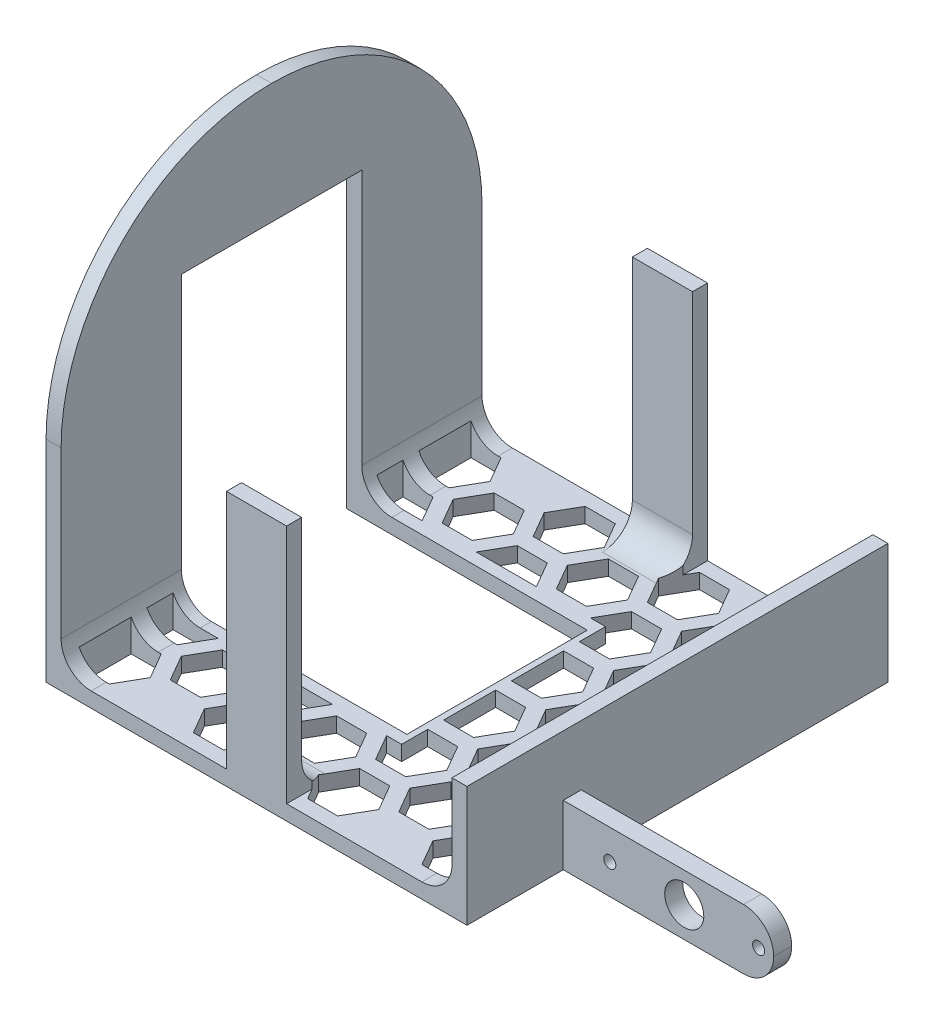
SolidWorks part; units mm, degrees
ref_plane "Front Plane" through (0, 0, 0) normal (0, 0, 1) x (1, 0, 0)
ref_plane "Top Plane" through (0, 0, 0) normal (0, 1, 0) x (1, 0, 0)
ref_plane "Right Plane" through (0, 0, 0) normal (1, 0, 0) x (0, 0, -1)
sketch "Sketch1" plane through (0, 0, 0) normal (0, 1, 0) x (1, 0, 0)
  line L1 (-35, -35) -> (35, -35)
  line L2 (-35, -35) -> (-35, 35)
  line L3 (-35, 35) -> (35, 35)
  line L4 (35, -35) -> (35, 35)
  line L5 (-35, -35) -> (35, 35) construction
  line L6 (-35, 35) -> (35, -35) construction
  point P0 (0, 0)
  dimension "D1" = 70
  dimension "D2" = 70
extrude "Boss-Extrude1" add sketch "Sketch1" along normal blind 70
sketch "Sketch2" plane through (0, 70, 0) normal (0, 1, 0) x (1, 0, 0)
  line L1 (-32.5, -32.5) -> (32.5, -32.5)
  line L2 (-32.5, -32.5) -> (-32.5, 32.5)
  line L3 (-32.5, 32.5) -> (32.5, 32.5)
  line L4 (32.5, -32.5) -> (32.5, 32.5)
  line L5 (-32.5, -32.5) -> (32.5, 32.5) construction
  line L6 (-32.5, 32.5) -> (32.5, -32.5) construction
  point P0 (0, 0)
  dimension "D1" = 65
  dimension "D2" = 65
extrude "Cut-Extrude1" cut sketch "Sketch2" against normal blind 67.5
sketch "Sketch3" plane through (35, 0, 0) normal (1, 0, 0) x (0, 0, -1)
  line L0 (-35, 70) -> (35, 70) construction
  line L1 (-32.5, 70) -> (32.5, 70)
  line L2 (-32.5, 70) -> (-32.5, 20)
  line L3 (-32.5, 20) -> (32.5, 20)
  line L4 (32.5, 70) -> (32.5, 20)
  line L5 (-35, 70) -> (-35, 0) construction
  dimension "D1" = 65
  dimension "D2" = 50
  dimension "D3" = 2.5
extrude "Cut-Extrude2" cut sketch "Sketch3" against normal blind 65
sketch "Sketch4" plane through (-35, 0, 0) normal (-1, 0, 0) x (0, 0, 1)
  line L0 (-35, 0) -> (35, 0) construction
  line L1 (-15, 0) -> (15, 0)
  line L2 (-15, 0) -> (-15, 50)
  line L3 (-15, 50) -> (15, 50)
  line L4 (15, 0) -> (15, 50)
  line L5 (-35, 70) -> (-35, 0) construction
  dimension "D1" = 30
  dimension "D2" = 20
  dimension "D3" = 50
extrude "Cut-Extrude3" cut sketch "Sketch4" against normal blind 40 and the other way blind 70
sketch "Sketch7" plane through (35, 0, 0) normal (1, 0, 0) x (0, 0, -1)
  line L0 (-35, 0) -> (35, 0) construction
  line L1 (-16, 0) -> (-19, 0)
  line L2 (-16, 0) -> (-16, 10)
  line L3 (-16, 10) -> (-19, 10)
  line L4 (-19, 0) -> (-19, 10)
  point P6 (0, 0)
  dimension "D1" = 3
  dimension "D2" = 16
  dimension "D3" = 10
extrude "Boss-Extrude3" add sketch "Sketch7" along normal blind 35
sketch "Sketch11" plane through (0, 0, -35) normal (0, 0, -1) x (-1, 0, 0)
  line L1 (-32.5, 2.5) -> (-5, 2.5)
  line L2 (-32.5, 2.5) -> (-32.5, 20)
  line L3 (-32.5, 82.5) -> (-5, 82.5)
  line L4 (-5, 2.5) -> (-5, 42.5)
  line L5 (35, 70) -> (35, 0) construction
  line L6 (32.5, 2.5) -> (5, 2.5)
  line L7 (32.5, 2.5) -> (32.5, 82.5)
  line L8 (32.5, 82.5) -> (5, 82.5)
  line L9 (5, 2.5) -> (5, 42.5)
  line L10 (-35, 70) -> (-35, 0) construction
  line L11 (-35, 0) -> (35, 0) construction
  line L12 (-32.5, 20) -> (-37.722, 20)
  line L13 (-37.722, 20) -> (-37.722, 82.5)
  line L14 (-37.722, 82.5) -> (-32.5, 82.5)
  line L15 (-5, 82.5) -> (5, 82.5)
  line L16 (-5, 42.5) -> (5, 42.5)
  dimension "D1" = 80
  dimension "D2" = 80
  dimension "D3" = 10
  dimension "D4" = 27.5
  dimension "D5" = 2.5
  dimension "D6" = 2.5
  dimension "D7" = 2.5
  dimension "D8" = 2.5
  dimension "D9" = 62.5
  dimension "D10" = 40
extrude "Cut-Extrude5" cut sketch "Sketch11" against normal through all
fillet "Fillet2" radius 35 2 edges at (-33.75, 70, 35) (-33.75, 70, -35)
sketch "Sketch12" plane through (0, 0, 16) normal (0, 0, -1) x (-1, 0, 0)
  line L0 (-70, 0) -> (-70, 10) construction
  line L1 (-70, 0) -> (-35, 0) construction
  circle A0 centre (-67.5, 5) radius 1
  circle A1 centre (-42.75, 5) radius 1
  circle A2 centre (-55.125, 5) radius 3.25
  dimension "D3" = 2
  dimension "D4" = 2
  dimension "D5" = 12.375
  dimension "D6" = 5
  dimension "D7" = 5
  dimension "D9" = 6.5
  dimension "D1" = 24.75
  dimension "D2" = 2.5
  dimension "D8" = 5
extrude "Cut-Extrude6" cut sketch "Sketch12" against normal blind 27.5
fillet "Fillet3" radius 5 2 edges at (70, 0, 17.5) (70, 10, 17.5)
sketch "Sketch13" plane through (0, 2.5, 0) normal (0, 1, 0) x (1, 0, 0)
  line L0 (13.5, -28.1699) -> (11, -23.8397)
  line L1 (32.5, -35) -> (32.5, 35) construction
  line L2 (32.5, -28.1699) -> (30, -23.8397)
  line L3 (30, -23.8397) -> (25, -23.8397)
  line L4 (25, -23.8397) -> (22.5, -28.1699)
  line L5 (22.5, -28.1699) -> (25, -32.5)
  line L6 (25, -32.5) -> (30, -32.5)
  line L7 (23, -22.5064) -> (20.5, -18.1763)
  line L8 (30, -32.5) -> (32.5, -28.1699)
  line L9 (20.5, -18.1763) -> (15.5, -18.1763)
  line L10 (32.5, -35) -> (5, -35) construction
  line L11 (15.5, -18.1763) -> (13, -22.5064)
  line L12 (13, -22.5064) -> (15.5, -26.8365)
  line L13 (15.5, -26.8365) -> (20.5, -26.8365)
  line L14 (20.5, -26.8365) -> (23, -22.5064)
  line L15 (11, -23.8397) -> (6, -23.8397)
  line L16 (6, -23.8397) -> (3.5, -28.1699)
  line L17 (3.5, -28.1699) -> (6, -32.5)
  line L18 (6, -32.5) -> (11, -32.5)
  line L19 (4, -22.5064) -> (1.5, -18.1763)
  line L20 (11, -32.5) -> (13.5, -28.1699)
  line L21 (1.5, -18.1763) -> (-3.5, -18.1763)
  line L22 (-3.5, -18.1763) -> (-6, -22.5064)
  line L23 (-6, -22.5064) -> (-3.5, -26.8365)
  line L24 (-3.5, -26.8365) -> (1.5, -26.8365)
  line L25 (1.5, -26.8365) -> (4, -22.5064)
  line L26 (-5.5, -28.1699) -> (-8, -23.8397)
  line L27 (-8, -23.8397) -> (-13, -23.8397)
  line L28 (-13, -23.8397) -> (-15.5, -28.1699)
  line L29 (-15.5, -28.1699) -> (-13, -32.5)
  line L30 (-13, -32.5) -> (-8, -32.5)
  line L31 (-15, -22.5064) -> (-17.5, -18.1763)
  line L32 (-8, -32.5) -> (-5.5, -28.1699)
  line L33 (-17.5, -18.1763) -> (-22.5, -18.1763)
  line L34 (-22.5, -18.1763) -> (-25, -22.5064)
  line L35 (-25, -22.5064) -> (-22.5, -26.8365)
  line L36 (-22.5, -26.8365) -> (-17.5, -26.8365)
  line L37 (-17.5, -26.8365) -> (-15, -22.5064)
  line L38 (-24.5, -28.1699) -> (-27, -23.8397)
  line L39 (-27, -23.8397) -> (-32, -23.8397)
  line L40 (-32, 32.6603) -> (-32, 24)
  line L41 (-32, 21.3603) -> (-32, 17.0301)
  line L42 (-32, -32.5) -> (-27, -32.5)
  line L43 (-32, 17.0301) -> (-24.5, 17.0301)
  line L44 (-27, -32.5) -> (-24.5, -28.1699)
  line L45 (-15.5, 17.0301) -> (-5.5, 17.0301)
  line L46 (3.5, 17.0301) -> (6, 17.0301)
  line L47 (6, 17.0301) -> (6, 12.7)
  line L48 (6, 10.0603) -> (6, 1.4)
  line L49 (6, -1.2397) -> (6, -9.9)
  line L50 (13.5, -16.8699) -> (11, -12.5397)
  line L51 (11, -12.5397) -> (6, -12.5397)
  line L52 (6, -12.5397) -> (6, -16.8699)
  line L53 (3.5, -16.8699) -> (6, -21.2)
  line L54 (6, -21.2) -> (11, -21.2)
  line L55 (6, -16.8699) -> (3.5, -16.8699)
  line L56 (11, -21.2) -> (13.5, -16.8699)
  line L57 (-5.5, -16.8699) -> (-15.5, -16.8699)
  line L58 (-24.5, -16.8699) -> (-32, -16.8699)
  line L59 (-32, -16.8699) -> (-32, -21.2)
  line L60 (-32, -23.8397) -> (-32, -32.5)
  line L65 (-15.5, -16.8699) -> (-13, -21.2)
  line L66 (-13, -21.2) -> (-8, -21.2)
  line L68 (-8, -21.2) -> (-5.5, -16.8699)
  line L78 (-32, -21.2) -> (-27, -21.2)
  line L80 (-27, -21.2) -> (-24.5, -16.8699)
  line L86 (13.5, -5.5699) -> (11, -1.2397)
  line L87 (11, -1.2397) -> (6, -1.2397)
  line L90 (6, -9.9) -> (11, -9.9)
  line L92 (11, -9.9) -> (13.5, -5.5699)
  line L122 (13.5, 5.7301) -> (11, 10.0603)
  line L123 (11, 10.0603) -> (6, 10.0603)
  line L126 (6, 1.4) -> (11, 1.4)
  line L128 (11, 1.4) -> (13.5, 5.7301)
  line L158 (13.5, 17.0301) -> (11, 21.3603)
  line L159 (11, 21.3603) -> (6, 21.3603)
  line L160 (6, 21.3603) -> (3.5, 17.0301)
  line L162 (6, 12.7) -> (11, 12.7)
  line L163 (4, 22.6936) -> (1.5, 27.0237)
  line L164 (11, 12.7) -> (13.5, 17.0301)
  line L165 (1.5, 27.0237) -> (-3.5, 27.0237)
  line L166 (-3.5, 27.0237) -> (-6, 22.6936)
  line L167 (-6, 22.6936) -> (-3.5, 18.3635)
  line L168 (-3.5, 18.3635) -> (1.5, 18.3635)
  line L169 (1.5, 18.3635) -> (4, 22.6936)
  line L170 (-5.5, 17.0301) -> (-8, 21.3603)
  line L171 (-8, 21.3603) -> (-13, 21.3603)
  line L172 (-13, 21.3603) -> (-15.5, 17.0301)
  line L175 (-15, 22.6936) -> (-17.5, 27.0237)
  line L177 (-17.5, 27.0237) -> (-22.5, 27.0237)
  line L178 (-22.5, 27.0237) -> (-25, 22.6936)
  line L179 (-25, 22.6936) -> (-22.5, 18.3635)
  line L180 (-22.5, 18.3635) -> (-17.5, 18.3635)
  line L181 (-17.5, 18.3635) -> (-15, 22.6936)
  line L182 (-24.5, 17.0301) -> (-27, 21.3603)
  line L183 (-27, 21.3603) -> (-32, 21.3603)
  line L194 (13.5, 28.3301) -> (11, 32.6603)
  line L195 (11, 32.6603) -> (6, 32.6603)
  line L196 (6, 32.6603) -> (3.5, 28.3301)
  line L197 (3.5, 28.3301) -> (6, 24)
  line L198 (6, 24) -> (11, 24)
  line L200 (11, 24) -> (13.5, 28.3301)
  line L206 (-5.5, 28.3301) -> (-8, 32.6603)
  line L207 (-8, 32.6603) -> (-13, 32.6603)
  line L208 (-13, 32.6603) -> (-15.5, 28.3301)
  line L209 (-15.5, 28.3301) -> (-13, 24)
  line L210 (-13, 24) -> (-8, 24)
  line L212 (-8, 24) -> (-5.5, 28.3301)
  line L218 (-24.5, 28.3301) -> (-27, 32.6603)
  line L219 (-27, 32.6603) -> (-32, 32.6603)
  line L222 (-32, 24) -> (-27, 24)
  line L224 (-27, 24) -> (-24.5, 28.3301)
  line L230 (32.5, -16.8699) -> (30, -12.5397)
  line L231 (30, -12.5397) -> (25, -12.5397)
  line L232 (25, -12.5397) -> (22.5, -16.8699)
  line L233 (22.5, -16.8699) -> (25, -21.2)
  line L234 (25, -21.2) -> (30, -21.2)
  line L235 (23, -11.2064) -> (20.5, -6.8763)
  line L236 (30, -21.2) -> (32.5, -16.8699)
  line L237 (20.5, -6.8763) -> (15.5, -6.8763)
  line L238 (15.5, -6.8763) -> (13, -11.2064)
  line L239 (13, -11.2064) -> (15.5, -15.5365)
  line L240 (15.5, -15.5365) -> (20.5, -15.5365)
  line L241 (20.5, -15.5365) -> (23, -11.2064)
  line L242 (32.5, -5.5699) -> (30, -1.2397)
  line L243 (30, -1.2397) -> (25, -1.2397)
  line L244 (25, -1.2397) -> (22.5, -5.5699)
  line L245 (22.5, -5.5699) -> (25, -9.9)
  line L246 (25, -9.9) -> (30, -9.9)
  line L247 (23, 0.0936) -> (20.5, 4.4237)
  line L248 (30, -9.9) -> (32.5, -5.5699)
  line L249 (20.5, 4.4237) -> (15.5, 4.4237)
  line L250 (15.5, 4.4237) -> (13, 0.0936)
  line L251 (13, 0.0936) -> (15.5, -4.2365)
  line L252 (15.5, -4.2365) -> (20.5, -4.2365)
  line L253 (20.5, -4.2365) -> (23, 0.0936)
  line L254 (32.5, 5.7301) -> (30, 10.0603)
  line L255 (30, 10.0603) -> (25, 10.0603)
  line L256 (25, 10.0603) -> (22.5, 5.7301)
  line L257 (22.5, 5.7301) -> (25, 1.4)
  line L258 (25, 1.4) -> (30, 1.4)
  line L259 (23, 11.3936) -> (20.5, 15.7237)
  line L260 (30, 1.4) -> (32.5, 5.7301)
  line L261 (20.5, 15.7237) -> (15.5, 15.7237)
  line L262 (15.5, 15.7237) -> (13, 11.3936)
  line L263 (13, 11.3936) -> (15.5, 7.0635)
  line L264 (15.5, 7.0635) -> (20.5, 7.0635)
  line L265 (20.5, 7.0635) -> (23, 11.3936)
  line L266 (32.5, 17.0301) -> (30, 21.3603)
  line L267 (30, 21.3603) -> (25, 21.3603)
  line L268 (25, 21.3603) -> (22.5, 17.0301)
  line L269 (22.5, 17.0301) -> (25, 12.7)
  line L270 (25, 12.7) -> (30, 12.7)
  line L271 (23, 22.6936) -> (20.5, 27.0237)
  line L272 (30, 12.7) -> (32.5, 17.0301)
  line L273 (20.5, 27.0237) -> (15.5, 27.0237)
  line L274 (15.5, 27.0237) -> (13, 22.6936)
  line L275 (13, 22.6936) -> (15.5, 18.3635)
  line L276 (15.5, 18.3635) -> (20.5, 18.3635)
  line L277 (20.5, 18.3635) -> (23, 22.6936)
  line L278 (32.5, 28.3301) -> (30, 32.6603)
  line L279 (30, 32.6603) -> (25, 32.6603)
  line L280 (25, 32.6603) -> (22.5, 28.3301)
  line L281 (22.5, 28.3301) -> (25, 24)
  line L282 (25, 24) -> (30, 24)
  line L284 (30, 24) -> (32.5, 28.3301)
  line L290 (-15, 33.9936) -> (-17.5, 38.3237) [skipped]
  line L291 (-17.5, 38.3237) -> (-22.5, 38.3237) [skipped]
  line L292 (-22.5, 38.3237) -> (-25, 33.9936) [skipped]
  line L293 (-25, 33.9936) -> (-22.5, 29.6635) [skipped]
  line L294 (-17.5, 29.6635) -> (-15, 33.9936) [skipped]
  line L295 (-22.5, 29.6635) -> (-17.5, 29.6635) [skipped]
  line L296 (-34, 33.9936) -> (-36.5, 38.3237) [skipped]
  line L297 (-36.5, 38.3237) -> (-41.5, 38.3237) [skipped]
  line L298 (-41.5, 38.3237) -> (-44, 33.9936) [skipped]
  line L299 (-44, 33.9936) -> (-41.5, 29.6635) [skipped]
  line L300 (-41.5, 29.6635) -> (-36.5, 29.6635) [skipped]
  line L301 (-36.5, 29.6635) -> (-34, 33.9936) [skipped]
  line L302 (4, 33.9936) -> (1.5, 38.3237) [skipped]
  line L303 (1.5, 38.3237) -> (-3.5, 38.3237) [skipped]
  line L304 (-3.5, 38.3237) -> (-6, 33.9936) [skipped]
  line L305 (-6, 33.9936) -> (-3.5, 29.6635) [skipped]
  line L306 (1.5, 29.6635) -> (4, 33.9936) [skipped]
  line L307 (-3.5, 29.6635) -> (1.5, 29.6635) [skipped]
  line L308 (23, 33.9936) -> (20.5, 38.3237) [skipped]
  line L309 (20.5, 38.3237) -> (15.5, 38.3237) [skipped]
  line L310 (15.5, 38.3237) -> (13, 33.9936) [skipped]
  line L311 (13, 33.9936) -> (15.5, 29.6635) [skipped]
  line L312 (20.5, 29.6635) -> (23, 33.9936) [skipped]
  line L313 (15.5, 29.6635) -> (20.5, 29.6635) [skipped]
  line L314 (-36.5, -18.1763) -> (-41.5, -18.1763) [skipped]
  line L315 (-41.5, -18.1763) -> (-44, -22.5064) [skipped]
  line L316 (-44, -22.5064) -> (-41.5, -26.8365) [skipped]
  line L317 (-41.5, -26.8365) -> (-36.5, -26.8365) [skipped]
  line L318 (-36.5, -6.8763) -> (-41.5, -6.8763) [skipped]
  line L319 (-41.5, -6.8763) -> (-44, -11.2064) [skipped]
  line L320 (-44, -11.2064) -> (-41.5, -15.5365) [skipped]
  line L321 (-41.5, -15.5365) -> (-36.5, -15.5365) [skipped]
  line L322 (-36.5, 4.4237) -> (-41.5, 4.4237) [skipped]
  line L323 (-41.5, 4.4237) -> (-44, 0.0936) [skipped]
  line L324 (-44, 0.0936) -> (-41.5, -4.2365) [skipped]
  line L325 (-41.5, -4.2365) -> (-36.5, -4.2365) [skipped]
  line L326 (-36.5, 15.7237) -> (-41.5, 15.7237) [skipped]
  line L327 (-41.5, 15.7237) -> (-44, 11.3936) [skipped]
  line L328 (-44, 11.3936) -> (-41.5, 7.0635) [skipped]
  line L329 (-41.5, 7.0635) -> (-36.5, 7.0635) [skipped]
  line L330 (-36.5, 27.0237) -> (-41.5, 27.0237) [skipped]
  line L331 (-41.5, 27.0237) -> (-44, 22.6936) [skipped]
  line L332 (-44, 22.6936) -> (-41.5, 18.3635) [skipped]
  line L333 (-41.5, 18.3635) -> (-36.5, 18.3635) [skipped]
  line L334 (-34, 22.6936) -> (-36.5, 27.0237) [skipped]
  line L335 (-36.5, 18.3635) -> (-34, 22.6936) [skipped]
  line L336 (-34, 11.3936) -> (-36.5, 15.7237) [skipped]
  line L337 (-36.5, 7.0635) -> (-34, 11.3936) [skipped]
  line L338 (-34, 0.0936) -> (-36.5, 4.4237) [skipped]
  line L339 (-36.5, -4.2365) -> (-34, 0.0936) [skipped]
  line L340 (-34, -11.2064) -> (-36.5, -6.8763) [skipped]
  line L341 (-36.5, -15.5365) -> (-34, -11.2064) [skipped]
  line L342 (-34, -22.5064) -> (-36.5, -18.1763) [skipped]
  line L343 (-36.5, -26.8365) -> (-34, -22.5064) [skipped]
  line L344 (4, -11.2064) -> (1.5, -6.8763) [skipped]
  line L345 (1.5, -6.8763) -> (-3.5, -6.8763) [skipped]
  line L346 (-3.5, -6.8763) -> (-6, -11.2064) [skipped]
  line L347 (-8, -12.5397) -> (-13, -12.5397) [skipped]
  line L348 (-15, -11.2064) -> (-17.5, -6.8763) [skipped]
  line L349 (-17.5, -6.8763) -> (-22.5, -6.8763) [skipped]
  line L350 (-22.5, -6.8763) -> (-25, -11.2064) [skipped]
  line L351 (-27, -12.5397) -> (-32, -12.5397) [skipped]
  line L352 (4, 0.0936) -> (1.5, 4.4237) [skipped]
  line L353 (1.5, 4.4237) -> (-3.5, 4.4237) [skipped]
  line L354 (-3.5, 4.4237) -> (-6, 0.0936) [skipped]
  line L355 (-6, 0.0936) -> (-3.5, -4.2365) [skipped]
  line L356 (-3.5, -4.2365) -> (1.5, -4.2365) [skipped]
  line L357 (1.5, -4.2365) -> (4, 0.0936) [skipped]
  line L358 (-5.5, -5.5699) -> (-8, -1.2397) [skipped]
  line L359 (-8, -1.2397) -> (-13, -1.2397) [skipped]
  line L360 (-13, -1.2397) -> (-15.5, -5.5699) [skipped]
  line L361 (-15.5, -5.5699) -> (-13, -9.9) [skipped]
  line L362 (-13, -9.9) -> (-8, -9.9) [skipped]
  line L363 (-15, 0.0936) -> (-17.5, 4.4237) [skipped]
  line L364 (-8, -9.9) -> (-5.5, -5.5699) [skipped]
  line L365 (-17.5, 4.4237) -> (-22.5, 4.4237) [skipped]
  line L366 (-22.5, 4.4237) -> (-25, 0.0936) [skipped]
  line L367 (-25, 0.0936) -> (-22.5, -4.2365) [skipped]
  line L368 (-22.5, -4.2365) -> (-17.5, -4.2365) [skipped]
  line L369 (-17.5, -4.2365) -> (-15, 0.0936) [skipped]
  line L370 (-24.5, -5.5699) -> (-27, -1.2397) [skipped]
  line L371 (-27, -1.2397) -> (-32, -1.2397) [skipped]
  line L372 (-32, -1.2397) -> (-34.5, -5.5699) [skipped]
  line L373 (-34.5, -5.5699) -> (-32, -9.9) [skipped]
  line L374 (-32, -9.9) -> (-27, -9.9) [skipped]
  line L375 (-27, -9.9) -> (-24.5, -5.5699) [skipped]
  line L376 (-6, 11.3936) -> (-3.5, 7.0635) [skipped]
  line L377 (-3.5, 7.0635) -> (1.5, 7.0635) [skipped]
  line L378 (1.5, 7.0635) -> (4, 11.3936) [skipped]
  line L379 (-5.5, 5.7301) -> (-8, 10.0603) [skipped]
  line L380 (-8, 10.0603) -> (-13, 10.0603) [skipped]
  line L381 (-13, 10.0603) -> (-15.5, 5.7301) [skipped]
  line L382 (-15.5, 5.7301) -> (-13, 1.4) [skipped]
  line L383 (-13, 1.4) -> (-8, 1.4) [skipped]
  line L384 (-8, 1.4) -> (-5.5, 5.7301) [skipped]
  line L385 (-25, 11.3936) -> (-22.5, 7.0635) [skipped]
  line L386 (-22.5, 7.0635) -> (-17.5, 7.0635) [skipped]
  line L387 (-17.5, 7.0635) -> (-15, 11.3936) [skipped]
  line L388 (-24.5, 5.7301) -> (-27, 10.0603) [skipped]
  line L389 (-27, 10.0603) -> (-32, 10.0603) [skipped]
  line L390 (-32, 10.0603) -> (-34.5, 5.7301) [skipped]
  line L391 (-34.5, 5.7301) -> (-32, 1.4) [skipped]
  line L392 (-32, 1.4) -> (-27, 1.4) [skipped]
  line L393 (-27, 1.4) -> (-24.5, 5.7301) [skipped]
  line L394 (-13, 12.7) -> (-8, 12.7) [skipped]
  line L395 (-32, 12.7) -> (-27, 12.7) [skipped]
  line L396 (-6, -11.2064) -> (-3.5, -15.5365) [skipped]
  line L397 (-3.5, -15.5365) -> (1.5, -15.5365) [skipped]
  line L398 (1.5, -15.5365) -> (4, -11.2064) [skipped]
  line L399 (-25, -11.2064) -> (-22.5, -15.5365) [skipped]
  line L400 (-22.5, -15.5365) -> (-17.5, -15.5365) [skipped]
  line L401 (-17.5, -15.5365) -> (-15, -11.2064) [skipped]
  line L402 (6, -12.5397) -> (3.5, -16.8699) [skipped]
  line L403 (-5.5, -16.8699) -> (-8, -12.5397) [skipped]
  line L404 (-13, -12.5397) -> (-15.5, -16.8699) [skipped]
  line L405 (-24.5, -16.8699) -> (-27, -12.5397) [skipped]
  line L406 (-32, -12.5397) -> (-34.5, -16.8699) [skipped]
  line L407 (6, -1.2397) -> (3.5, -5.5699) [skipped]
  line L408 (3.5, -5.5699) -> (6, -9.9) [skipped]
  line L409 (6, 10.0603) -> (3.5, 5.7301) [skipped]
  line L410 (3.5, 5.7301) -> (6, 1.4) [skipped]
  line L411 (3.5, 17.0301) -> (6, 12.7) [skipped]
  line L412 (4, 11.3936) -> (1.5, 15.7237) [skipped]
  line L413 (1.5, 15.7237) -> (-3.5, 15.7237) [skipped]
  line L414 (-3.5, 15.7237) -> (-6, 11.3936) [skipped]
  line L415 (-15, 11.3936) -> (-17.5, 15.7237) [skipped]
  line L416 (-17.5, 15.7237) -> (-22.5, 15.7237) [skipped]
  line L417 (-22.5, 15.7237) -> (-25, 11.3936) [skipped]
  line L418 (-15.5, 17.0301) -> (-13, 12.7) [skipped]
  line L419 (-8, 12.7) -> (-5.5, 17.0301) [skipped]
  line L420 (-34.5, 17.0301) -> (-32, 12.7) [skipped]
  line L421 (-27, 12.7) -> (-24.5, 17.0301) [skipped]
  line L422 (-32, -23.8397) -> (-34.5, -28.1699) [skipped]
  line L423 (-34.5, -28.1699) -> (-32, -32.5) [skipped]
  line L424 (-34.5, -16.8699) -> (-32, -21.2) [skipped]
  line L425 (-32, 21.3603) -> (-34.5, 17.0301) [skipped]
  line L426 (-32, 32.6603) -> (-34.5, 28.3301) [skipped]
  line L427 (-34.5, 28.3301) -> (-32, 24) [skipped]
  dimension "D3" = 2.5
  dimension "D1" = 5
  dimension "D2" = 0
  dimension "D4" = 5
  dimension "D5" = 1.3333
  dimension "D6" = 2
  dimension "D7" = 4
  dimension "D8" = 6
extrude "Cut-Extrude7" cut sketch "Sketch13" against normal blind 27.5
fillet "Fillet4" radius 5 11 edges at (0, 2.5, -32.5) (0, 2.5, 32.5) (32.5, 2.5, 31.5849) (32.5, 2.5, 22.5199) (32.5, 2.5, 11.2199) (32.5, 2.5, -31.6651) (32.5, 2.5, -22.6801) (32.5, 2.5, -11.3801) (32.5, 2.5, -0.0801) (-32.5, 2.5, -25) (-32.5, 2.5, 25)
